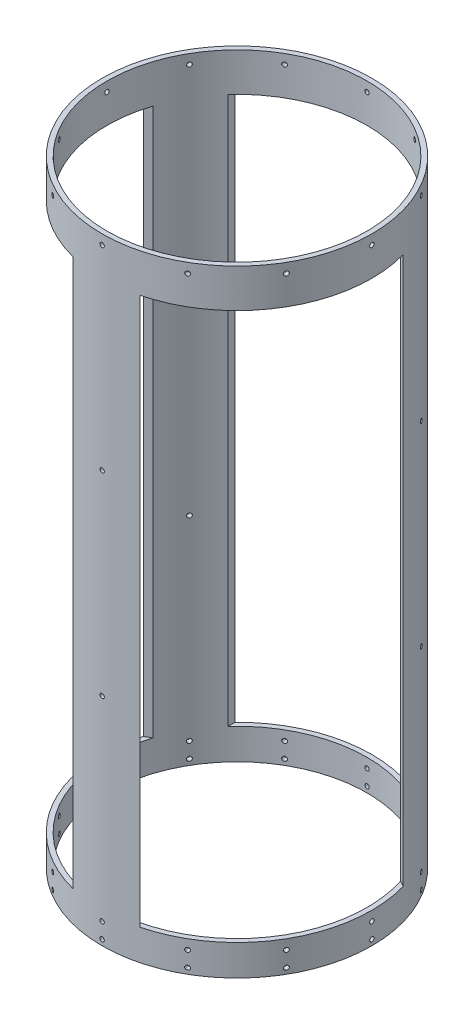
SolidWorks part; units mm, degrees
material "6061-T6 (SS)"
ref_plane "Front Plane" through (0, 0, 0) normal (0, 0, 1) x (1, 0, 0)
ref_plane "Top Plane" through (0, 0, 0) normal (0, 1, 0) x (1, 0, 0)
ref_plane "Right Plane" through (0, 0, 0) normal (1, 0, 0) x (0, 0, -1)
sketch "Sketch1" plane through (0, 0, 0) normal (0, 1, 0) x (1, 0, 0)
  circle A0 centre (0, 0) radius 88.9
  circle A1 centre (0, 0) radius 85.725
  dimension "D1" = 177.8
  dimension "D2" = 171.45
extrude "Boss-Extrude1" add sketch "Sketch1" along normal mid plane 406.4
sketch "Sketch2" plane through (0, 0, 0) normal (0, 0, 1) x (1, 0, 0)
  line L0 (85.725, 203.2) -> (-85.725, 203.2) construction
  line L1 (-63.5, -182.88) -> (63.5, -182.88)
  line L2 (-63.5, -182.88) -> (-63.5, 177.8)
  line L3 (-63.5, 177.8) -> (63.5, 177.8)
  line L4 (63.5, -182.88) -> (63.5, 177.8)
  line L5 (-63.5, -182.88) -> (63.5, 177.8) construction
  line L6 (-63.5, 177.8) -> (63.5, -182.88) construction
  line L7 (88.9, -203.2) -> (88.9, 203.2) construction
  line L8 (-88.9, 203.2) -> (-88.9, -203.2) construction
  line L9 (-88.9, -203.2) -> (88.9, -203.2) construction
  point P0 (0, 0)
  dimension "D1" = 25.4
  dimension "D2" = 25.4
  dimension "D3" = 25.4
  dimension "D4" = 20.32
extrude "Cut-Extrude1" cut sketch "Sketch2" against normal up to surface (62.217 mm away) up to face at (0, 203.2, 88.9)
pattern_circular "CirPattern1" count 3 over 360 about axis through (0, 203.2, 0) along (0, -1, 0) of "Cut-Extrude1"
ref_plane "Plane1" through (88.9, 0, 0) normal (1, 0, 0) x (0, 0, -1)
sketch "Sketch3" plane through (88.9, 0, 0) normal (1, 0, 0) x (0, 0, -1)
  line L0 (23.8841, -182.88) -> (-86.1011, -182.88) construction
  line L1 (-88.9, -203.2) -> (88.9, -203.2) construction
  circle A0 centre (0, -199.39) radius 1.4351
  circle A1 centre (0, -189.23) radius 1.4351
  dimension "D1" = 3.81
  dimension "D2" = 2.8702
  dimension "D3" = 2.8702
  dimension "D4" = 6.35
extrude "Cut-Extrude2" cut sketch "Sketch3" against normal blind 15.24
pattern_circular "CirPattern2" count 12 over 360 about axis through (0, 203.2, 0) along (0, -1, 0) of "Cut-Extrude2" reverse direction yes
sketch "Sketch4" plane through (88.9, 0, 0) normal (1, 0, 0) x (0, 0, -1)
  line L0 (0, 97.79) -> (0, -97.79) construction
  line L1 (88.9, 203.2) -> (-88.9, 203.2) construction
  circle A0 centre (0, 196.85) radius 1.4351
  dimension "D1" = 2.8702
  dimension "D2" = 6.35
extrude "Cut-Extrude3" cut sketch "Sketch4" against normal blind 15.24
pattern_circular "CirPattern3" count 12 over 360 about axis through (0, 203.2, 0) along (0, -1, 0) of "Cut-Extrude3"
ref_plane "Plane2" through (0, 0, 88.9) normal (0, 0, 1) x (1, 0, 0)
sketch "Sketch5" plane through (0, 0, 88.9) normal (0, 0, 1) x (1, 0, 0)
  circle A0 centre (0, 68.1736) radius 1.4351
  circle A1 centre (0, -60.5536) radius 1.4351
  circle A2 centre (0, 196.85) radius 1.4351 construction
  circle A3 centre (0, -189.23) radius 1.4351 construction
  dimension "D1" = 128.6764
  dimension "D2" = 128.6764
  dimension "D3" = 2.8702
  dimension "D4" = 2.8702
extrude "Cut-Extrude4" cut sketch "Sketch5" against normal blind 35.56
pattern_circular "CirPattern4" count 3 over 360 about axis through (0, 203.2, 0) along (0, -1, 0) of "Cut-Extrude4"
